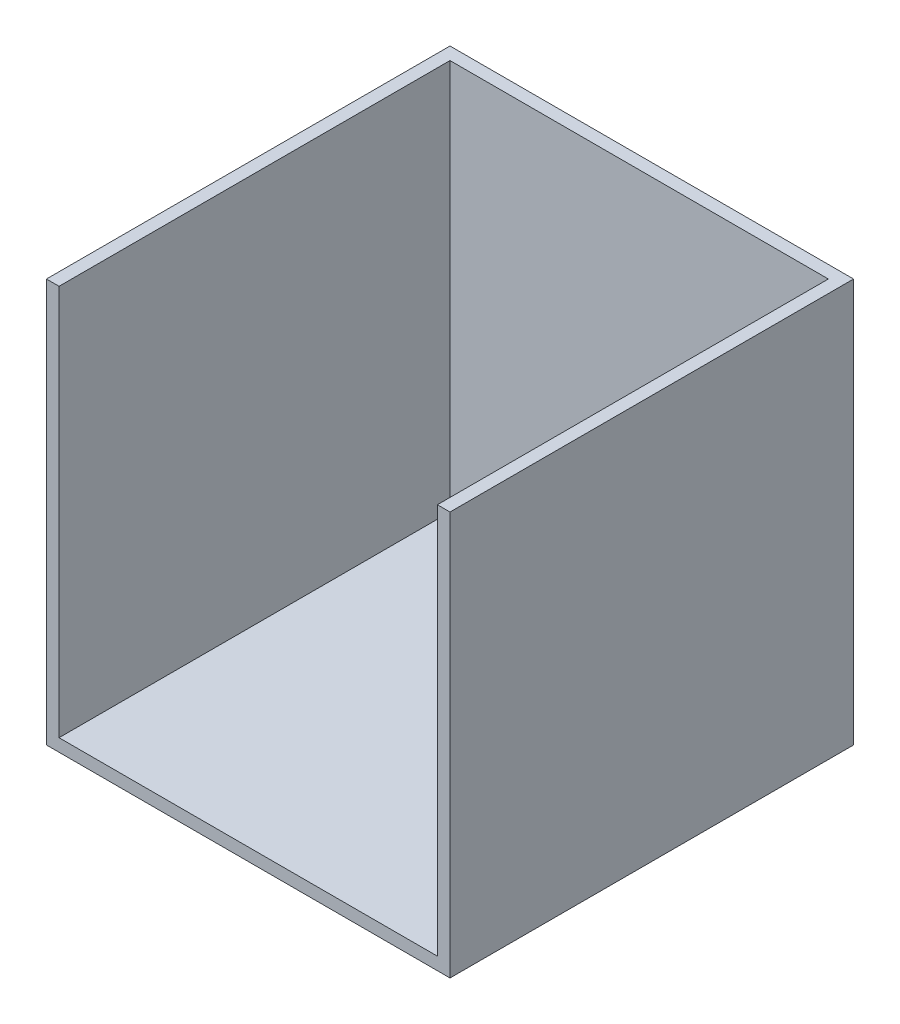
SolidWorks part; units mm, degrees
ref_plane "Front Plane" through (0, 0, 0) normal (0, 0, 1) x (1, 0, 0)
ref_plane "Top Plane" through (0, 0, 0) normal (0, 1, 0) x (1, 0, 0)
ref_plane "Right Plane" through (0, 0, 0) normal (1, 0, 0) x (0, 0, -1)
sketch "Sketch1" plane through (0, 0, 0) normal (0, 0, 1) x (1, 0, 0)
  line L1 (-152.4, -152.4) -> (152.4, -152.4)
  line L2 (-152.4, -152.4) -> (-152.4, 152.4)
  line L3 (-152.4, 152.4) -> (152.4, 152.4)
  line L4 (152.4, -152.4) -> (152.4, 152.4)
  line L5 (-152.4, -152.4) -> (152.4, 152.4) construction
  line L6 (-152.4, 152.4) -> (152.4, -152.4) construction
  point P0 (0, 0)
  dimension "D1" = 304.8
  dimension "D2" = 304.8
extrude "Boss-Extrude1" add sketch "Sketch1" along normal blind 304.8
shell "Shell1" thickness 9.525 removed face at (0, 0, 304.8) removed face at (0, 152.4, 152.4)
